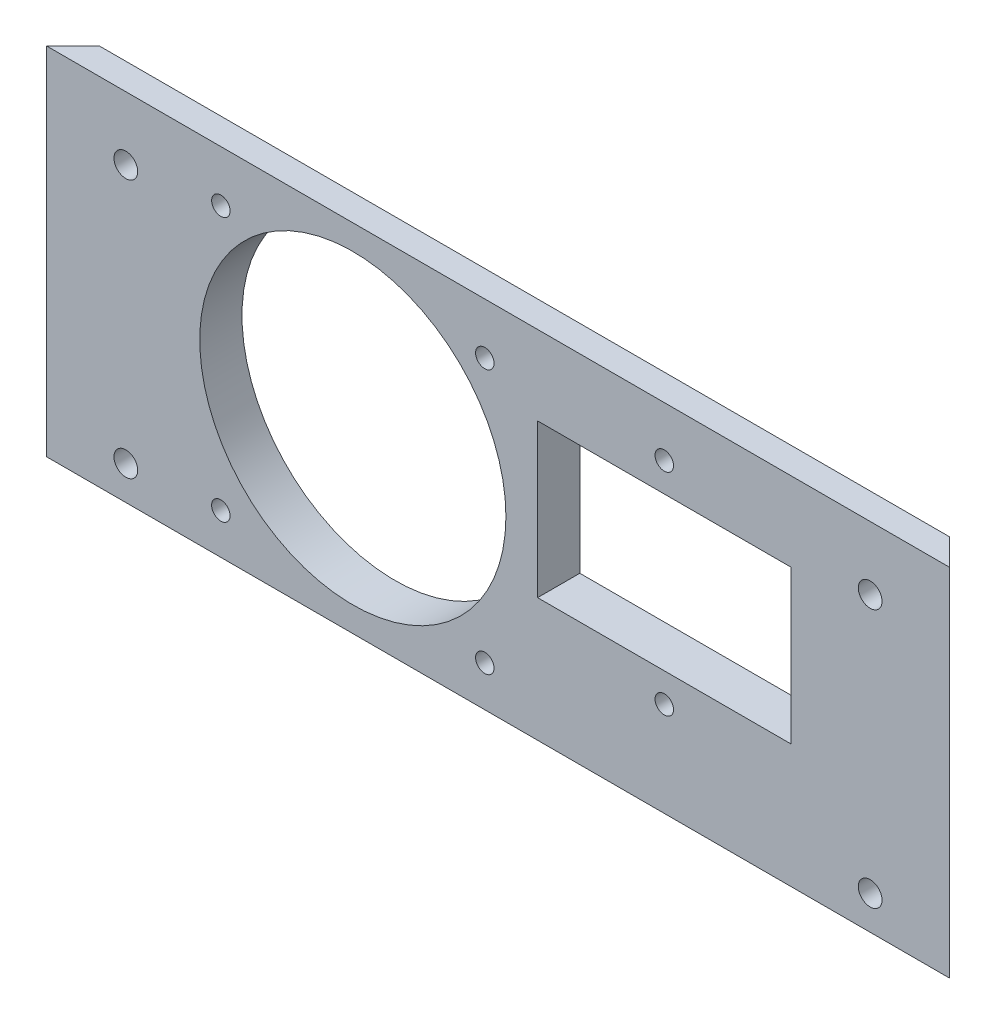
SolidWorks part; units mm, degrees
ref_plane "Front Plane" through (0, 0, 0) normal (0, 0, 1) x (1, 0, 0)
ref_plane "Top Plane" through (0, 0, 0) normal (0, 1, 0) x (1, 0, 0)
ref_plane "Right Plane" through (0, 0, 0) normal (1, 0, 0) x (0, 0, -1)
sketch "Sketch1" plane through (0, 0, 0) normal (0, 0, 1) x (1, 0, 0)
  line L0 (85.5, 70) -> (85.5, -37.3998) construction
  line L1 (0, 0) -> (171, 0)
  line L2 (0, 0) -> (0, 70)
  line L3 (0, 70) -> (171, 70)
  line L4 (171, 0) -> (171, 70)
  line L5 (0, 35) -> (171, 35) construction
  circle A0 centre (15, 9) radius 2.25
  circle A1 centre (156, 9) radius 2.25
  circle A4 centre (15, 58) radius 2.25
  circle A5 centre (156, 58) radius 2.25
  dimension "D3" = 15
  dimension "D5" = 4.5
  dimension "D1" = 70
  dimension "D2" = 171
  dimension "D4" = 9
  dimension "D6" = 2
  dimension "D7" = 12
extrude "Boss-Extrude1" add sketch "Sketch1" against normal blind 5
sketch "Sketch2" plane through (0, 0, -5) normal (0, 0, -1) x (-1, 0, 0)
  line L0 (0, 0) -> (-171, 0) construction
  line L1 (0, 0) -> (-171, 0) construction
  line L2 (0, 5) -> (-171, 5)
  line L3 (-171, 5) -> (-171, 70)
  line L4 (-171, 70) -> (0, 70)
  line L5 (0, 70) -> (0, 5)
  circle A1 centre (-15, 9) radius 2.25 construction
  circle A2 centre (-156, 9) radius 2.25 construction
  circle A5 centre (-15, 9) radius 2.25
  circle A6 centre (-156, 9) radius 2.25
  circle A8 centre (-15, 58) radius 2.25 construction
  circle A9 centre (-156, 58) radius 2.25 construction
  circle A10 centre (-15, 58) radius 2.25
  circle A11 centre (-156, 58) radius 2.25
  dimension "D1" = 5
extrude "Boss-Extrude2" add sketch "Sketch2" along normal blind 3
chamfer "Chamfer1" distance 8 angle 45 3 edges at (171, 37.5, -8) (0, 37.5, -8) (85.5, 70, -8)
chamfer "Chamfer3" distance 3 angle 45 1 edges at (85.5, 70, -8)
sketch "Sketch3" plane through (85.5, 0, -85.5) normal (0.7071, 0, -0.7071) x (-0.7071, 0, -0.7071)
  line L0 (-120.9153, 0) -> (-120.9153, 2.6)
  line L1 (-120.9153, 0) -> (-120.9153, 70) construction
  line L2 (-120.9153, 2.6) -> (-113.8442, 2.6)
  line L4 (-113.8442, 2.6) -> (-113.8442, 0)
  line L5 (-113.8442, 0) -> (-120.9153, 0)
  line L6 (-109.6016, 5) -> (-113.8442, 5) construction
  dimension "D1" = 2.4
extrude "Cut-Extrude1" cut sketch "Sketch3" along direction (1, 0, 0) on the side against the normal through all
sketch "Sketch4" plane through (0, 0, 0) normal (0, 0, 1) x (1, 0, 0)
  line L0 (171, 70) -> (0, 70) construction
  line L1 (93, 26) -> (141, 26)
  line L2 (93, 26) -> (93, 55)
  line L3 (93, 55) -> (141, 55)
  line L4 (141, 26) -> (141, 55)
  line L5 (171, 2.6) -> (171, 70) construction
  line L6 (117, 60.5) -> (117, 20.5) construction
  line L7 (93, 40.5) -> (141, 40.5) construction
  line L8 (29, 36.3) -> (28, 36.3) construction
  line L9 (28, 36.3) -> (28, 65.3) construction
  line L10 (28, 65.3) -> (58, 65.3) construction
  line L11 (28, 60.3) -> (33, 60.3) construction
  line L12 (33, 60.3) -> (33, 65.3) construction
  circle A0 centre (58, 36.3) radius 29
  circle A1 centre (33, 60.3) radius 1.75
  circle A2 centre (83, 60.3) radius 1.75
  circle A3 centre (83, 10.3) radius 1.75
  circle A4 centre (33, 10.3) radius 1.75
  circle A5 centre (117, 60.5) radius 1.75
  circle A6 centre (117, 20.5) radius 1.75
  point P28 (117, 40.5)
  point P31 (117, 55)
  dimension "D5" = 58
  dimension "D6" = 33.7
  dimension "D8" = 5
  dimension "D11" = 3.5
  dimension "D16" = 0
  dimension "D1" = 29
  dimension "D2" = 48
  dimension "D3" = 15
  dimension "D4" = 30
  dimension "D7" = 35
  dimension "D9" = 5
  dimension "D10" = 1
  dimension "D14" = 40
  dimension "D15" = 0
  dimension "D12" = 2
  dimension "D13" = 2
extrude "Cut-Extrude2" cut sketch "Sketch4" against normal through all
